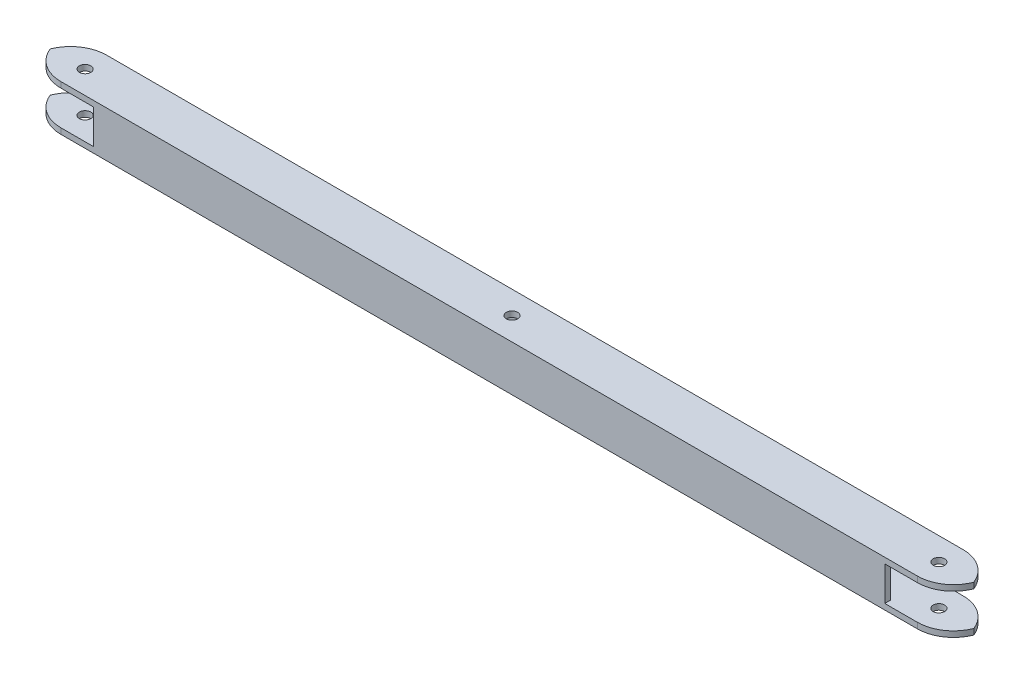
SolidWorks part; units mm, degrees
ref_plane "Front Plane" through (0, 0, 0) normal (0, 0, 1) x (1, 0, 0)
ref_plane "Top Plane" through (0, 0, 0) normal (0, 1, 0) x (1, 0, 0)
ref_plane "Right Plane" through (0, 0, 0) normal (1, 0, 0) x (0, 0, -1)
sketch "Sketch1" plane through (0, 0, 0) normal (0, 1, 0) x (1, 0, 0)
  line L0 (0, 0) -> (515.5, 0)
  line L1 (515.5, 0) -> (515.5, -25.4)
  line L2 (515.5, -25.4) -> (0, -25.4)
  line L3 (0, -25.4) -> (0, 0)
  line L4 (257.75, 0) -> (257.75, -25.4) construction
  line L5 (0, -12.7) -> (515.5, -12.7) construction
  circle A3 centre (257.75, -12.7) radius 3.175
  circle A6 centre (20.76, -12.7) radius 3.175
  circle A8 centre (494.74, -12.7) radius 3.175
  circle A9 centre (20.76, -12.7) radius 3.175 construction
  dimension "D3" = 6.35
  dimension "D5" = 236.99
  dimension "D4" = 6.35
  dimension "D1" = 515.5
  dimension "D2" = 25.4
extrude "Boss-Extrude1" add sketch "Sketch1" along normal blind 25.4
sketch "Sketch2" plane through (0, 0, 0) normal (-1, 0, 0) x (0, 0, 1)
  line L14 (3.175, 22.225) -> (3.175, 3.175)
  line L15 (3.175, 3.175) -> (22.225, 3.175)
  line L16 (22.225, 3.175) -> (22.225, 22.225)
  line L17 (22.225, 22.225) -> (3.175, 22.225)
  line L18 (3.175, 22.225) -> (3.175, 3.175)
  line L19 (3.175, 3.175) -> (22.225, 3.175)
  line L20 (22.225, 3.175) -> (22.225, 22.225)
  line L21 (22.225, 22.225) -> (3.175, 22.225)
  dimension "D1" = 3.175
extrude "Cut-Extrude1" cut sketch "Sketch2" against normal up to surface (515.5 mm away) up to face at (515.5, 12.7, 12.7)
sketch "Sketch4" plane through (0, 0, 0) normal (-1, 0, 0) x (0, 0, 1)
  line L1 (25.4, 25.4) -> (25.4, 0) construction
  line L2 (25.4, 22.225) -> (25.4, 3.175)
  line L3 (25.4, 3.175) -> (0, 3.175)
  line L4 (0, 25.4) -> (0, 0) construction
  line L5 (0, 3.175) -> (0, 22.225)
  line L7 (0, 22.225) -> (25.4, 22.225)
  line L8 (0, 25.4) -> (25.4, 25.4) construction
  line L9 (3.175, 3.175) -> (22.225, 3.175) construction
  dimension "D2" = 3.175
extrude "Cut-Extrude2" cut sketch "Sketch4" against normal blind 38.1
ref_plane "Plane1" through (257.75, 0, 0) normal (-1, 0, 0) x (0, 0, 1)
mirror "Mirror1" about plane through (257.75, 0, 0) normal (-1, 0, 0) of "Cut-Extrude2"
fillet "Fillet1" radius 20 8 edges at (515.5, 1.5875, 0) (515.5, 23.8125, 0) (515.5, 1.5875, 25.4) (515.5, 23.8125, 25.4) (0, 1.5875, 25.4) (0, 23.8125, 25.4) (0, 1.5875, 0) (0, 23.8125, 0)
sketch "Sketch5" plane through (0, 25.4, 0) normal (0, 1, 0) x (1, 0, 0)
  circle A0 centre (20.76, -12.7) radius 3.175 construction
  circle A1 centre (494.74, -12.7) radius 3.175 construction
